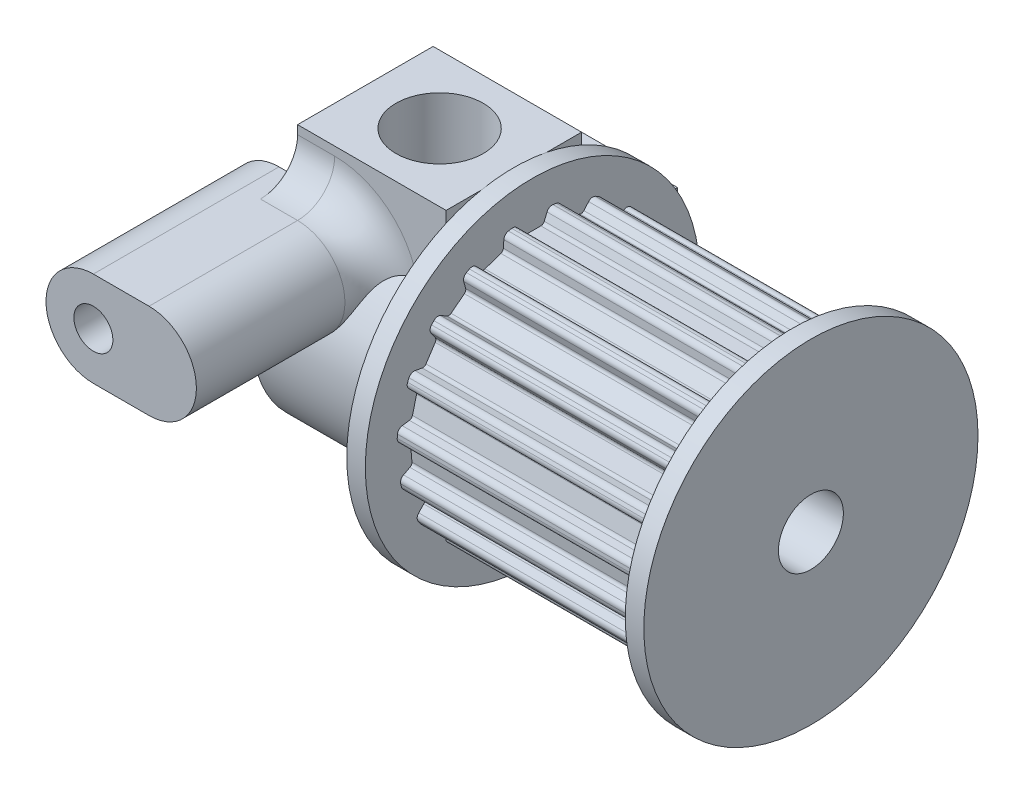
SolidWorks part; units mm, degrees
material "PLA Black"
ref_plane "Front" through (0, 0, 0) normal (0, 0, 1) x (1, 0, 0)
ref_plane "Top" through (0, 0, 0) normal (0, 1, 0) x (1, 0, 0)
ref_plane "Right" through (0, 0, 0) normal (1, 0, 0) x (0, 0, -1)
sketch "Sketch1" plane through (0, 0, 0) normal (1, 0, 0) x (0, 0, -1)
  line L0 (1.118, 1) -> (-1.118, 1) construction
  line L1 (-3.65, 4.8249) -> (3.65, 4.8249)
  line L2 (4.8249, 3.65) -> (4.8249, -3.65)
  line L3 (0, 0) -> (11.6334, 0) construction
  line L4 (0, 0) -> (0, 8.6732) construction
  arc A0 (-1.118, 1) -> (1.118, 1) centre (0, 0) ccw construction
  circle A1 centre (0, 0) radius 1.75
  arc A2 (4.8249, -3.65) -> (-3.65, 4.8249) centre (0, 0) cw
  arc A3 (4.8249, 3.65) -> (3.65, 4.8249) centre (0, 0) ccw
  dimension "D1" = 3
  dimension "D3" = 0.25
  dimension "D5" = 6.05
  dimension "D2" = 1
  dimension "D4" = 7.3
extrude "Boss-Extrude1" add sketch "Sketch1" along normal mid plane 8
sketch "Sketch2" plane through (0, 4.8249, 0) normal (0, 1, 0) x (1, 0, 0)
  circle A0 centre (0, 0) radius 2.35
  dimension "D1" = 4.7
extrude "Cut-Extrude1" cut sketch "Sketch2" against normal blind 5
sketch "Sketch7" plane through (4, 0, 0) normal (1, 0, 0) x (0, 0, -1)
  circle A0 centre (0, 0) radius 1.75 construction
  circle A1 centre (0, 0) radius 7.3
  circle A2 centre (0, 0) radius 1.75
  dimension "D1" = 14.6
extrude "Boss-Extrude5" add sketch "Sketch7" along normal blind 15
sketch "Sketch8" plane through (19, 0, 0) normal (1, 0, 0) x (0, 0, -1)
  line L0 (-0.4541, 6.5499) -> (0.4528, 6.5499)
  line L1 (0.6374, 6.6734) -> (0.7865, 7.0333)
  line L2 (-0.6389, 6.6734) -> (-0.788, 7.0333)
  line L6 (0, 9.2013) -> (0, 0) construction
  arc A0 (0.4528, 6.5499) -> (0.6374, 6.6734) centre (0.4526, 6.7499) ccw
  arc A1 (-0.4541, 6.5499) -> (-0.6389, 6.6734) centre (-0.4541, 6.7499) cw
  arc A2 (0.7865, 7.0333) -> (1.1093, 7.2152) centre (1.0638, 6.9187) cw
  arc A3 (-0.788, 7.0333) -> (-1.1108, 7.215) centre (-1.0652, 6.9185) ccw
  circle A4 centre (0, 0) radius 7.3 construction
  arc A5 (-1.1108, 7.215) -> (1.1093, 7.2152) centre (0, 0) cw
  point P3 (-0.0007, 6.5499)
  point P15 (0, 9.84)
extrude "Cut-Extrude3" cut sketch "Sketch8" against normal up to surface (15 mm away) up to face at (4, 0, -7.3)
pattern_circular "CirPattern1" count 19 over 360 about axis through (19, 0, 0) along (-1, 0, 0) of "Cut-Extrude3"
sketch "Sketch9" plane through (19, 0, 0) normal (1, 0, 0) x (0, 0, -1)
  circle A0 centre (0, 0) radius 9
  circle A1 centre (0, 0) radius 1.75 construction
  circle A2 centre (0, 0) radius 1.75
  dimension "D1" = 18
extrude "Boss-Extrude6" add sketch "Sketch9" along normal blind 1
sketch "Sketch10" plane through (4, 0, 0) normal (-1, 0, 0) x (0, 0, 1)
  circle A0 centre (0, 0) radius 9
  circle A1 centre (0, 0) radius 9 construction
  circle A2 centre (0, 0) radius 1.75 construction
  circle A3 centre (0, 0) radius 1.75
extrude "Boss-Extrude7" add sketch "Sketch10" against normal blind 1
sketch "Sketch3" plane through (0, 0, -4.8249) normal (0, 0, -1) x (-1, 0, 0)
  circle A0 centre (0, 0) radius 2.35
  dimension "D1" = 4.7
extrude "Cut-Extrude2" cut sketch "Sketch3" against normal blind 5
sketch "Sketch4" plane through (0, 4.8249, 0) normal (0, 1, 0) x (1, 0, 0)
  line L0 (4, 3.65) -> (-4, 3.65) construction
  line L2 (4, -3.65) -> (-4, -3.65) construction
  line L3 (-4, 3.65) -> (-4, -3.65) construction
  line L4 (4, 3.65) -> (-4, 3.65)
  line L5 (4, 3.65) -> (4, -3.65)
  line L6 (4, -3.65) -> (-4, -3.65)
  line L7 (-4, 3.65) -> (-4, -3.65)
  line L8 (4, 7.3) -> (4, -7.3) construction
  circle A0 centre (0, 0) radius 2.35 construction
  circle A1 centre (0, 0) radius 2.35
extrude "Boss-Extrude2" add sketch "Sketch4" along normal blind 4
sketch "Sketch5" plane through (0, 0, -4.8249) normal (0, 0, -1) x (-1, 0, 0)
  line L0 (-4, 3.65) -> (4, 3.65) construction
  line L1 (4, -3.65) -> (4, 3.65) construction
  line L2 (-4, -3.65) -> (4, -3.65) construction
  line L4 (-4, 3.65) -> (4, 3.65)
  line L5 (4, -3.65) -> (4, 3.65)
  line L6 (-4, -3.65) -> (4, -3.65)
  line L7 (-4, -3.65) -> (-4, 3.65)
  line L8 (-4, -7.3) -> (-4, 7.3) construction
  circle A0 centre (0, 0) radius 2.35 construction
  circle A1 centre (0, 0) radius 2.35
extrude "Boss-Extrude3" add sketch "Sketch5" along normal blind 4
ref_axis "Axis1" through (20, 0, 0) along (-1, 0, 0)
sketch "Sketch6" plane through (0, 0, 3.65) normal (0, 0, 1) x (1, 0, 0)
  line L0 (-4, 8.8249) -> (-4, 4.8249) construction
  line L2 (-2, 6.3555) -> (-5, 6.3555)
  line L3 (-5, 1.2545) -> (-2, 1.2545)
  line L6 (20, 0) -> (-4, 0) construction
  circle A0 centre (-5, 3.805) radius 1.0505
  arc A1 (-5, 6.3555) -> (-5, 1.2545) centre (-5, 3.805) ccw
  arc A2 (-2, 6.3555) -> (-2, 1.2545) centre (-2, 3.805) cw
  dimension "D1" = 2.101
  dimension "D2" = 3.805
  dimension "D3" = 1.5
  dimension "D4" = 1
  dimension "D5" = 3
extrude "Boss-Extrude4" add sketch "Sketch6" along normal blind 10
fillet "Fillet1" radius 2 2 edges at (-0.6029, 5.9388, 3.65) (-3, 6.3555, 3.65)
equation "\"knee_angle\"= 70"
equation "\"ankle_angle\" = 80"
equation "\"hip_angle\" = 40"
equation "\"spring_ankle_parallel_arm_diameter\"= 1.5"
equation "\"spring_ankle_parallel_arm_length\"= 13"
equation "\"spring_ankle_parallel_intern_diameter\"= 5.7"
equation "\"spring_ankle_parallel_angle\"= \"ankle_angle\""
equation "\"spring_ankle_parallel_turns\"= 3"
equation "\"spring_ankle_parallel_pitch\"= \"spring_ankle_parallel_arm_diameter\" * 1.01"
equation "\"spring_ankle_parallel_cutting_distance\"= (1-\"spring_ankle_parallel_angle\" / 360) * \"spring_ankle_parallel_pitch\""
equation "\"spring_ankle_serial_arm_diameter\"= 1.91"
equation "\"spring_ankle_serial_arm_length\"= 10"
equation "\"spring_ankle_serial_intern_diameter\"= 5.7"
equation "\"spring_ankle_serial_angle\"= \"90\""
equation "\"spring_ankle_serial_turns\"= 3"
equation "\"spring_ankle_serial_pitch\"= \"spring_ankle_serial_arm_diameter\" * 1.01"
equation "\"spring_ankle_serial_cutting_distance\"= (1-\"spring_ankle_serial_angle\" / 360) * \"spring_ankle_serial_pitch\""
equation "\"spring_knee_parallel_arm_diameter\"= 1.5"
equation "\"spring_knee_parallel_arm_length\"= 13"
equation "\"spring_knee_parallel_intern_diameter\"= 5.7"
equation "\"spring_knee_parallel_angle\"= -\"knee_angle\" + 90"
equation "\"spring_knee_parallel_turns\"= 3"
equation "\"spring_knee_parallel_pitch\"= \"spring_knee_parallel_arm_diameter\" * 1.01"
equation "\"spring_knee_parallel_cutting_distance\"= (1-(\"spring_knee_parallel_angle\") / 360) * \"spring_knee_parallel_pitch\""
equation "\"spring_knee_serial_arm_diameter\"= 1.91"
equation "\"spring_knee_serial_arm_length\"= 10"
equation "\"spring_knee_serial_intern_diameter\"= 5.7"
equation "\"spring_knee_serial_angle\"= \"90\""
equation "\"spring_knee_serial_turns\"= 3"
equation "\"spring_knee_serial_pitch\"= \"spring_knee_serial_arm_diameter\" * 1.01"
equation "\"spring_knee_serial_cutting_distance\"= (1-\"spring_knee_serial_angle\" / 360) * \"spring_knee_serial_pitch\""
equation "\"D2@Sketch6\" = ( \"spring_ankle_serial_intern_diameter\" + \"spring_ankle_serial_arm_diameter\" ) / 2"
equation "\"D1@Sketch6\" = \"spring_ankle_serial_arm_diameter\" * 1.1"
